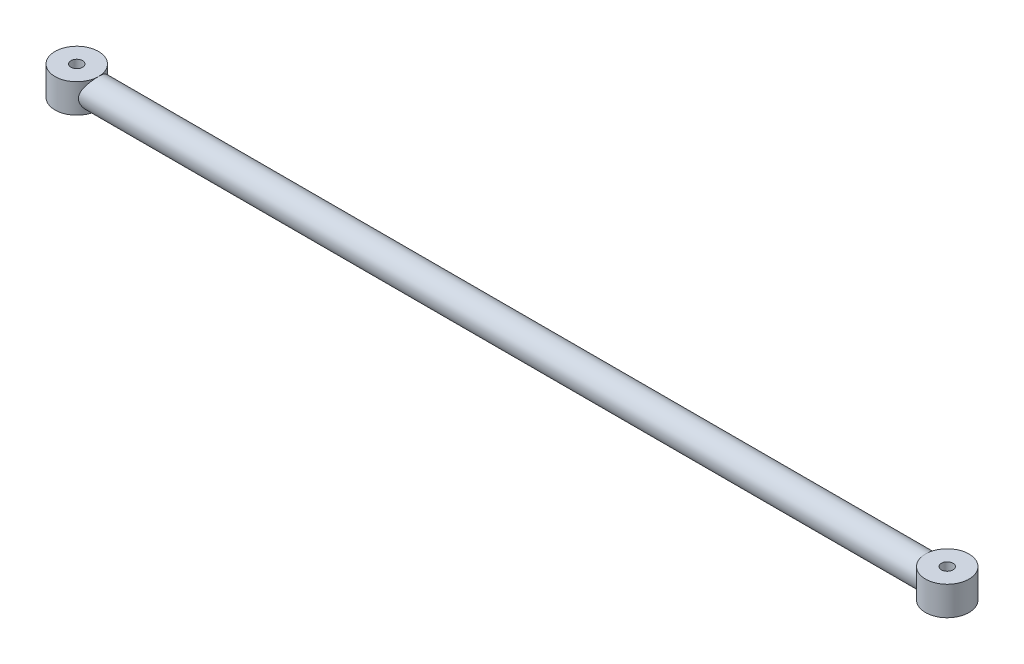
SolidWorks part; units mm, degrees
ref_plane "Front Plane" through (0, 0, 0) normal (0, 0, 1) x (1, 0, 0)
ref_plane "Top Plane" through (0, 0, 0) normal (0, 1, 0) x (1, 0, 0)
ref_plane "Right Plane" through (0, 0, 0) normal (1, 0, 0) x (0, 0, -1)
sketch "Sketch1" plane through (0, 0, 0) normal (0, 1, 0) x (1, 0, 0)
  line L0 (0, 0) -> (300, 0) construction
  circle A0 centre (0, 0) radius 7.5
  circle A1 centre (300, 0) radius 7.5
  circle A2 centre (0, 0) radius 2
  circle A3 centre (300, 0) radius 2
  dimension "D2" = 4
  dimension "D5" = 15
  dimension "D1" = 300
extrude "Boss-Extrude1" add sketch "Sketch1" along normal blind 10
ref_plane "Plane1" through (150, 0, 0) normal (1, 0, 0) x (0, 0, -1)
sketch "Sketch2" plane through (150, 0, 0) normal (1, 0, 0) x (0, 0, -1)
  line L0 (0, 0) -> (0, 5) construction
  circle A0 centre (0, 5) radius 5
  dimension "D2" = 10
  dimension "D1" = 5
extrude "Boss-Extrude2" add sketch "Sketch2" along normal up to surface and the other way up to surface up to face at (300, 10, 7.5) other way up to face at (0, 10, 7.5)
